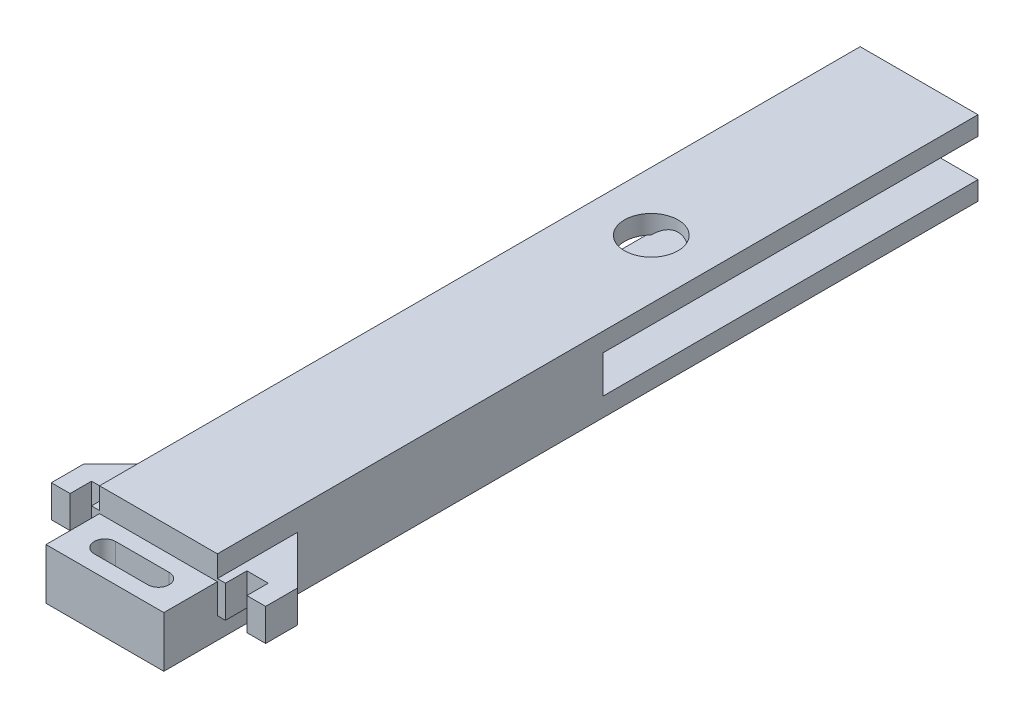
SolidWorks part; units mm, degrees
ref_plane "Front Plane" through (0, 0, 0) normal (0, 0, 1) x (1, 0, 0)
ref_plane "Top Plane" through (0, 0, 0) normal (0, 1, 0) x (1, 0, 0)
ref_plane "Right Plane" through (0, 0, 0) normal (1, 0, 0) x (0, 0, -1)
sketch "Sketch1" plane through (0, 0, 0) normal (0, 1, 0) x (1, 0, 0)
  line L1 (-5.5, 38) -> (5.5, 38)
  line L2 (-5.5, 38) -> (-5.5, -38)
  line L3 (-5.5, -38) -> (5.5, -38)
  line L4 (5.5, 38) -> (5.5, -38)
  line L5 (-5.5, 38) -> (5.5, -38) construction
  line L6 (-5.5, -38) -> (5.5, 38) construction
  point P0 (0, 0)
  dimension "D1" = 76
  dimension "D2" = 11
extrude "Boss-Extrude1" add sketch "Sketch1" along normal blind 7
ref_plane "Plane1" through (0, 0, 0) normal (-1, 0, 0) x (0, 0, 1)
sketch "Sketch3" plane through (0, 0, 0) normal (-1, 0, 0) x (0, 0, 1)
  line L0 (-38, 3.5) -> (28, 3.5)
  line L2 (38, 7) -> (38, 0) construction
  line L3 (-38, 7) -> (-38, 0) construction
  line L4 (31, 0.5) -> (31, 0)
  line L5 (-38, 0) -> (38, 0) construction
  arc A1 (31, 0.5) -> (28, 3.5) centre (28, 0.5) ccw
  point P9 (31, 3.5)
  point P14 (-38, 3.5)
  dimension "D1" = 3
  dimension "D2" = 7
sketch "Sketch4" plane through (0, 0, -38) normal (0, 0, -1) x (-1, 0, 0)
  line L0 (-5.5, 7) -> (-5.5, 0) construction
  line L1 (0, -55.5125) -> (0, 55.5125) construction
  circle A0 centre (0, 3.5) radius 2.5
  point P8 (-5.5, 3.5)
  dimension "D1" = 5
sweep "Cut-Sweep2" cut profiles "Sketch4" path "Sketch3"
sketch "Sketch5" plane through (-5.5, 0, 0) normal (-1, 0, 0) x (0, 0, 1)
  line L0 (38, 7) -> (38, 0) construction
  line L1 (30, 5) -> (33, 5)
  line L2 (30, 5) -> (30, 2)
  line L3 (30, 2) -> (33, 2)
  line L4 (33, 5) -> (33, 2)
  line L5 (30, 5) -> (33, 2) construction
  line L6 (30, 2) -> (33, 5) construction
  point P0 (31.5, 3.5)
  point P7 (38, 3.5)
  point P8 (33, 3.5)
  dimension "D1" = 3
  dimension "D2" = 5
extrude "Boss-Extrude2" add sketch "Sketch5" along normal blind 4.5
ref_plane "Plane2" through (0, 0, 0) normal (-1, 0, 0) x (0, 0, 1)
mirror "Mirror1" about plane through (0, 0, 0) normal (-1, 0, 0) of "Boss-Extrude2"
sketch "Sketch6" plane through (0, 0, 33) normal (0, 0, 1) x (1, 0, 0)
  line L0 (-10, 5) -> (-5.5, 5) construction
  line L1 (-8.25, 5) -> (-6.25, 5)
  line L2 (-8.25, 5) -> (-8.25, 2)
  line L3 (-8.25, 2) -> (-6.25, 2)
  line L4 (-6.25, 5) -> (-6.25, 2)
  line L5 (-8.25, 5) -> (-6.25, 2) construction
  line L6 (-8.25, 2) -> (-6.25, 5) construction
  line L7 (-10, 2) -> (-5.5, 2) construction
  line L8 (-5.5, 2) -> (-5.5, 5) construction
  point P0 (-7.25, 3.5)
  dimension "D1" = 0.75
  dimension "D2" = 2
extrude "Cut-Extrude2" cut sketch "Sketch6" against normal offset from surface (2 mm away) 1 up to face at (-7.75, 3.5, 30)
mirror "Mirror2" about plane through (0, 0, 0) normal (-1, 0, 0) of "Cut-Extrude2"
sketch "Sketch7" plane through (0, 5, 0) normal (0, 1, 0) x (1, 0, 0)
  line L0 (-10, -30) -> (-5.5, -25.5)
  line L1 (-5.5, 38) -> (-5.5, -38) construction
  line L2 (-5.5, -25.5) -> (-5.5, -30)
  line L3 (-5.5, -30) -> (-10, -30)
extrude "Boss-Extrude3" add sketch "Sketch7" against normal up to surface (3 mm away) up to face at (-7.5, 2, 31.75)
mirror "Mirror3" about plane through (0, 0, 0) normal (-1, 0, 0) of "Boss-Extrude3"
sketch "Sketch10" plane through (0, 0, -38) normal (0, 0, -1) x (-1, 0, 0)
  line L1 (-5.5, 5.25) -> (5.5, 5.25)
  line L2 (-5.5, 5.25) -> (-5.5, 1.75)
  line L3 (-5.5, 1.75) -> (5.5, 1.75)
  line L4 (5.5, 5.25) -> (5.5, 1.75)
  line L5 (-5.5, 5.25) -> (5.5, 1.75) construction
  line L6 (-5.5, 1.75) -> (5.5, 5.25) construction
  line L8 (-5.5, 7) -> (-5.5, 0) construction
  line L10 (5.5, 7) -> (5.5, 0) construction
  point P0 (0, 3.5)
  point P15 (-5.5, 3.5)
  dimension "D1" = 3.5
  dimension "D2" = 11
extrude "Cut-Extrude5" cut sketch "Sketch10" against normal blind 35
sketch "Sketch11" plane through (0, 7, 0) normal (0, 1, 0) x (1, 0, 0)
  line L0 (5.5, 38) -> (-5.5, 38) construction
  circle A0 centre (0, 13) radius 2.5
  dimension "D1" = 5
  dimension "D2" = 25
extrude "Cut-Extrude6" cut sketch "Sketch11" against normal up to next
sketch "Sketch12" plane through (0, 0, 38) normal (0, 0, 1) x (1, 0, 0)
  line L1 (-5.5, 7) -> (5.5, 7)
  line L2 (-5.5, 7) -> (-5.5, 4.75)
  line L3 (-5.5, 4.75) -> (5.5, 4.75)
  line L4 (5.5, 7) -> (5.5, 4.75)
  line L5 (5.5, 2) -> (5.5, 5) construction
  dimension "D1" = 2.25
  dimension "D2" = 11
extrude "Cut-Extrude9" cut sketch "Sketch12" against normal blind 5
sketch "Sketch15" plane through (0, 7, 0) normal (0, 1, 0) x (1, 0, 0)
  circle A0 centre (0, 13) radius 2.5
  circle A1 centre (0, 13) radius 4
  dimension "D1" = 1.5
extrude "Boss-Extrude4" [suppressed] add sketch "Sketch15" along normal blind 2.5
sketch "Sketch14" plane through (0, 4.75, 0) normal (0, 1, 0) x (1, 0, 0)
  line L0 (-2.5, -35.5) -> (2.5, -35.5) construction
  line L1 (-2.5, -34.5) -> (2.5, -34.5)
  line L2 (-2.5, -36.5) -> (2.5, -36.5)
  line L3 (-5.5, -38) -> (5.5, -38) construction
  line L4 (5.5, -33) -> (5.5, -38) construction
  arc A0 (-2.5, -34.5) -> (-2.5, -36.5) centre (-2.5, -35.5) ccw
  arc A1 (2.5, -36.5) -> (2.5, -34.5) centre (2.5, -35.5) ccw
  point P2 (0, -35.5)
  point P9 (0, -38)
  point P13 (5.5, -35.5)
  dimension "D2" = 5
  dimension "D1" = 2
extrude "Cut-Extrude10" cut sketch "Sketch14" against normal up to next
